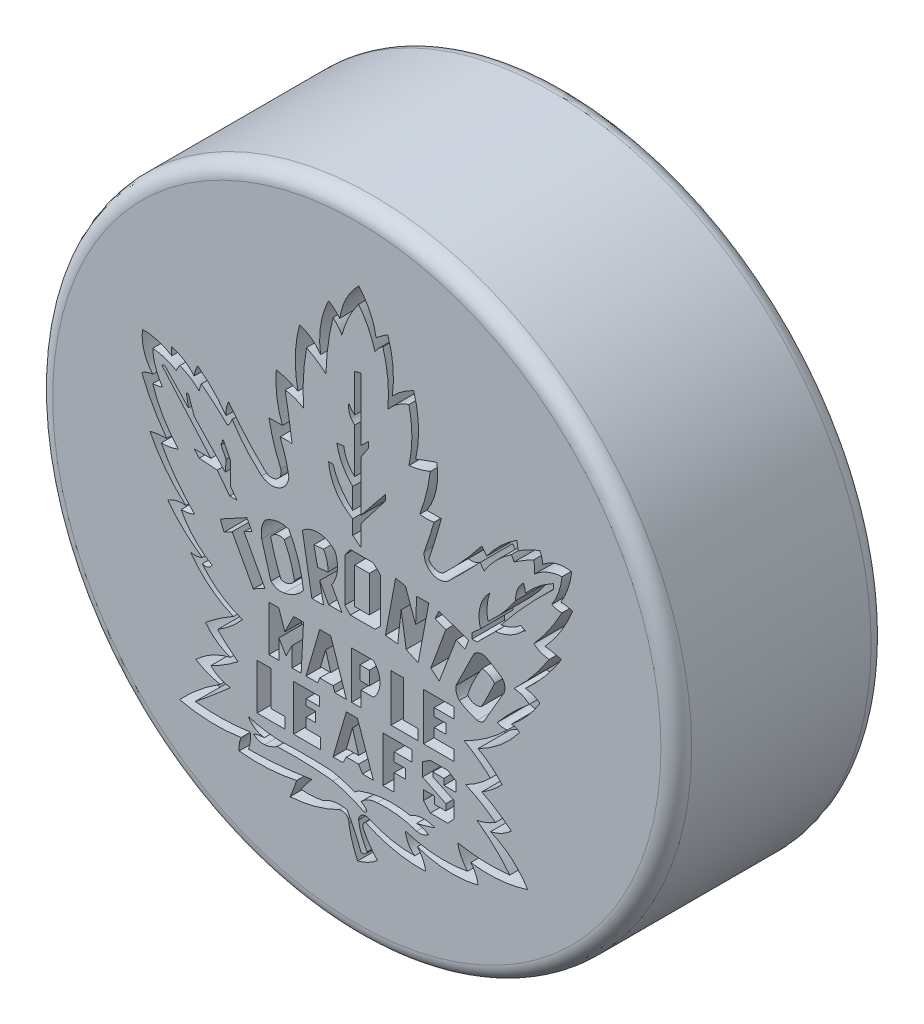
SolidWorks part; units mm, degrees
ref_plane "Front Plane" through (0, 0, 0) normal (0, 0, 1) x (1, 0, 0)
ref_plane "Top Plane" through (0, 0, 0) normal (0, 1, 0) x (1, 0, 0)
ref_plane "Right Plane" through (0, 0, 0) normal (1, 0, 0) x (0, 0, -1)
sketch "Sketch1" plane through (0, 0, 0) normal (0, 0, 1) x (1, 0, 0)
  line L0 (34.5, 121.5) -> (172.5, 121.5) construction
  line L1 (6.3057, 68.3336) -> (15.8951, 57.3506)
  line L6 (30.3167, 86.1583) -> (30.3167, 80.7546)
  line L7 (27.2525, 71.8253) -> (24.9367, 71.8253)
  line L8 (6.9514, 74.6669) -> (6.8534, 73.8865)
  line L9 (12.1754, 10.8034) -> (19.3568, 10.8034)
  line L10 (15.8951, 57.3506) -> (12.6238, 57.3506)
  line L11 (12.6238, 57.3506) -> (13.5994, 56.2333)
  line L12 (13.5994, 56.2333) -> (17.1344, 55.9938)
  line L13 (17.1344, 55.9938) -> (19.5676, 52.8135)
  line L14 (19.5676, 52.8135) -> (21.025, 52.8135)
  line L15 (21.025, 52.8135) -> (19.7407, 54.4922)
  line L16 (19.7407, 54.4922) -> (19.7407, 58.8908)
  line L17 (19.7407, 58.8908) -> (18.2642, 61.8099)
  line L18 (18.2642, 61.8099) -> (17.8765, 60.6287)
  line L19 (17.8765, 60.6287) -> (18.8654, 58.6737)
  line L20 (18.8654, 58.6737) -> (18.7132, 56.4273)
  line L21 (18.7132, 56.4273) -> (12.6238, 62.8421)
  line L22 (12.6238, 62.8421) -> (11.5036, 66.0747)
  line L25 (11.5036, 63.7081) -> (6.8096, 68.653)
  line L26 (6.8096, 68.653) -> (6.3057, 68.3336)
  line L27 (11.5036, 63.7081) -> (11.1004, 66.0747)
  line L28 (11.1004, 66.0747) -> (11.5036, 66.0747)
  line L29 (44.0339, 86.1583) -> (45.2677, 86.4828)
  line L30 (45.2677, 86.4828) -> (45.2677, 74.1922)
  line L31 (45.2677, 74.1922) -> (46.7323, 75.6568)
  line L32 (46.7323, 75.6568) -> (46.7323, 74.5052)
  line L33 (46.7323, 74.5052) -> (45.2677, 72.2648)
  line L34 (45.2677, 72.2648) -> (45.2677, 62.4102)
  line L35 (45.2677, 62.4102) -> (50.0411, 68.3336)
  line L36 (50.0411, 68.3336) -> (50.0411, 67.2036)
  line L37 (50.0411, 67.2036) -> (45.2677, 61.0086)
  line L38 (45.2677, 61.0086) -> (45.2677, 56.9127)
  line L39 (45.2677, 56.9127) -> (43.6367, 58.1694)
  line L40 (43.6367, 58.1694) -> (43.6367, 61.0086)
  line L41 (38.9245, 68.3336) -> (39.7941, 68.3336)
  line L42 (40.5155, 72.2648) -> (41.9224, 72.4343)
  line L43 (41.9224, 72.4343) -> (41.9224, 72.3332)
  line L44 (43.6367, 66.4741) -> (43.6367, 62.4102)
  line L45 (44.0339, 78.7841) -> (44.0339, 86.1583)
  line L46 (44.0339, 68.3336) -> (44.0339, 77.0681)
  line L48 (66.9786, 53.365) -> (66.9786, 52.2776)
  line L49 (66.9786, 52.2776) -> (67.9755, 52.2776)
  line L50 (67.9755, 52.2776) -> (71.5619, 55.8427)
  line L51 (66.9786, 53.365) -> (68.6517, 54.8561)
  line L52 (76.5056, 59.3605) -> (77.4165, 58.8908)
  line L53 (77.4165, 58.8908) -> (77.0329, 58.6853)
  line L54 (29.874, 69.9206) -> (27.2525, 69.9206)
  line L55 (17.7325, 48.0078) -> (22.922, 50.8265)
  line L56 (22.922, 50.8265) -> (23.9165, 48.9955)
  line L57 (23.9165, 48.9955) -> (22.3701, 48.1556)
  line L58 (22.3701, 48.1556) -> (26.4629, 40.6203)
  line L59 (26.4629, 40.6203) -> (24.1884, 39.3849)
  line L60 (24.1884, 39.3849) -> (20.0547, 46.9954)
  line L61 (20.0547, 46.9954) -> (18.4461, 46.1217)
  line L62 (18.4461, 46.1217) -> (17.7325, 48.0078)
  line L63 (42.0881, 54.1273) -> (42.0881, 45.5535)
  line L64 (42.0881, 45.5535) -> (43.1911, 44.4505)
  line L65 (43.1911, 44.4505) -> (48.0086, 44.4505)
  line L66 (48.0086, 44.4505) -> (49.1116, 45.5535)
  line L67 (49.1116, 45.5535) -> (49.1116, 54.1273)
  line L68 (49.1116, 54.1273) -> (47.6913, 55.5476)
  line L69 (47.6913, 55.5476) -> (43.1911, 55.5476)
  line L70 (43.1911, 55.5476) -> (42.0881, 54.1273)
  line L71 (44.0339, 53.365) -> (46.8868, 53.365)
  line L72 (46.8868, 53.365) -> (46.8868, 46.3139)
  line L73 (46.8868, 46.3139) -> (44.0339, 46.3139)
  line L74 (44.0339, 46.3139) -> (44.0339, 53.365)
  line L75 (33.7917, 54.1273) -> (35.6496, 43.498)
  line L76 (35.6496, 43.498) -> (37.933, 43.498)
  line L77 (37.933, 43.498) -> (37.1838, 47.2971)
  line L78 (37.1838, 47.2971) -> (38.9245, 44.0735)
  line L79 (38.9245, 44.0735) -> (41.5213, 44.0735)
  line L80 (41.5213, 44.0735) -> (39.5306, 47.7599)
  line L81 (36.0392, 52.7859) -> (36.7945, 49.3156)
  line L82 (36.7945, 49.3156) -> (38.7916, 49.5311)
  line L83 (36.0392, 52.7859) -> (37.933, 52.9837)
  line L84 (25.8383, 48.6827) -> (27.6283, 42.4266)
  line L85 (50.0411, 44.4505) -> (52.0362, 55.1267)
  line L86 (52.0362, 55.1267) -> (53.9533, 54.7684)
  line L87 (53.9533, 54.7684) -> (55.9534, 49.2355)
  line L88 (55.9534, 49.2355) -> (56.144, 54.1273)
  line L89 (56.144, 54.1273) -> (58.5251, 54.1273)
  line L90 (58.5251, 54.1273) -> (56.4417, 42.9794)
  line L91 (56.4417, 42.9794) -> (54.1026, 44.0735)
  line L92 (54.1026, 44.0735) -> (53.1196, 50.3069)
  line L93 (53.1196, 50.3069) -> (52.4464, 44.1881)
  line L94 (52.4464, 44.1881) -> (50.0411, 44.4505)
  line L96 (66.3288, 51.7517) -> (65.6176, 49.8908)
  line L97 (65.6176, 49.8908) -> (63.8591, 50.5629)
  line L98 (63.8591, 50.5629) -> (60.5679, 41.9509)
  line L99 (60.5679, 41.9509) -> (58.9206, 43.3234)
  line L100 (58.9206, 43.3234) -> (61.8601, 51.3268)
  line L101 (61.8601, 51.3268) -> (59.7442, 52.1039)
  line L103 (59.7442, 52.1039) -> (60.5123, 53.7569)
  line L104 (60.5123, 53.7569) -> (66.3288, 51.7517)
  line L105 (63.8591, 42.8783) -> (67.3185, 49.8908)
  line L106 (69.358, 39.5777) -> (73.2604, 46.3139)
  line L107 (27.2525, 29.7743) -> (27.2525, 38.6676)
  line L108 (27.2525, 38.6676) -> (29.1958, 38.6676)
  line L109 (29.1958, 38.6676) -> (30.3678, 35.2087)
  line L110 (30.3678, 35.2087) -> (32.0759, 38.6676)
  line L111 (32.0759, 38.6676) -> (34.0127, 38.6676)
  line L112 (34.0127, 38.6676) -> (33.5534, 29.7743)
  line L113 (33.5534, 29.7743) -> (31.7771, 29.7743)
  line L114 (31.7771, 29.7743) -> (31.7771, 33.586)
  line L115 (31.7771, 33.586) -> (30.6072, 31.2168)
  line L116 (30.6072, 31.2168) -> (29.1958, 33.586)
  line L117 (29.1958, 33.586) -> (29.1958, 29.7743)
  line L118 (29.1958, 29.7743) -> (27.2525, 29.7743)
  line L119 (34.4991, 29.7743) -> (36.7945, 29.7743)
  line L120 (36.7945, 29.7743) -> (37.1838, 30.7878)
  line L121 (37.1838, 30.7878) -> (39.7941, 30.7878)
  line L122 (39.7941, 30.7878) -> (40.1678, 29.7743)
  line L123 (40.1678, 29.7743) -> (42.3991, 29.7743)
  line L124 (42.3991, 29.7743) -> (39.3473, 39.0131)
  line L125 (39.3473, 39.0131) -> (37.1838, 39.0131)
  line L126 (37.1838, 39.0131) -> (34.4991, 29.7743)
  line L127 (37.3474, 32.7715) -> (39.3473, 32.7715)
  line L128 (39.3473, 32.7715) -> (38.3474, 36.1374)
  line L129 (38.3474, 36.1374) -> (37.3474, 32.7715)
  line L130 (43.4149, 29.7743) -> (43.4149, 39.0131)
  line L131 (43.4149, 39.0131) -> (47.6913, 39.0131)
  line L132 (43.4149, 29.7743) -> (45.2399, 29.7743)
  line L133 (45.2399, 29.7743) -> (45.2399, 32.7715)
  line L134 (45.2399, 32.7715) -> (47.6913, 32.7715)
  line L135 (51.1553, 39.0131) -> (53.5887, 39.0131)
  line L136 (45.0765, 36.9598) -> (46.8868, 36.9598)
  line L137 (45.0765, 36.9598) -> (45.0765, 34.2952)
  line L138 (45.0765, 34.2952) -> (46.8868, 34.2952)
  line L139 (46.8868, 36.9598) -> (46.8868, 34.2952)
  line L140 (53.5887, 39.0131) -> (53.5887, 31.8324)
  line L141 (53.5887, 31.8324) -> (56.4417, 31.8324)
  line L145 (51.1553, 39.0131) -> (51.1553, 29.7743)
  line L146 (51.1553, 29.7743) -> (56.4417, 29.7743)
  line L147 (56.4417, 29.7743) -> (56.4417, 31.8324)
  line L148 (57.4755, 29.7743) -> (63.4335, 29.7743)
  line L149 (63.4335, 29.7743) -> (63.4335, 31.8324)
  line L150 (63.4335, 31.8324) -> (59.5649, 31.8324)
  line L151 (59.5649, 31.8324) -> (59.5649, 33.586)
  line L152 (59.5649, 33.586) -> (61.8601, 33.586)
  line L153 (61.8601, 33.586) -> (61.8601, 35.4618)
  line L154 (61.8601, 35.4618) -> (59.5649, 35.4618)
  line L155 (59.5649, 35.4618) -> (59.5649, 36.9598)
  line L156 (59.5649, 36.9598) -> (63.4335, 36.9598)
  line L157 (63.4335, 36.9598) -> (63.4335, 39.0131)
  line L158 (63.4335, 39.0131) -> (57.4755, 39.0131)
  line L159 (57.4755, 39.0131) -> (57.4755, 29.7743)
  line L160 (24.9367, 27.6583) -> (27.6283, 27.6583)
  line L161 (27.6283, 27.6583) -> (27.6283, 20.8444)
  line L162 (27.6283, 20.8444) -> (30.3678, 20.8444)
  line L163 (30.3678, 20.8444) -> (30.3678, 18.7141)
  line L164 (30.3678, 18.7141) -> (24.9367, 18.7141)
  line L165 (24.9367, 18.7141) -> (24.9367, 27.6583)
  line L166 (32.0759, 27.6583) -> (32.0759, 18.7141)
  line L167 (32.0759, 18.7141) -> (37.3474, 18.7141)
  line L168 (37.3474, 18.7141) -> (37.3474, 20.8444)
  line L169 (37.3474, 20.8444) -> (34.4991, 20.8444)
  line L170 (34.4991, 20.8444) -> (34.4991, 22.8011)
  line L171 (34.4991, 22.8011) -> (36.3392, 22.8011)
  line L172 (36.3392, 22.8011) -> (36.3392, 24.7422)
  line L173 (36.3392, 24.7422) -> (34.4991, 24.7422)
  line L174 (34.4991, 24.7422) -> (34.4991, 25.9294)
  line L175 (34.4991, 25.9294) -> (37.1838, 25.9294)
  line L176 (37.1838, 25.9294) -> (37.1838, 27.6583)
  line L177 (37.1838, 27.6583) -> (32.0759, 27.6583)
  line L178 (39.7941, 18.7141) -> (41.7277, 18.7141)
  line L179 (41.7277, 18.7141) -> (42.3991, 19.9957)
  line L180 (42.3991, 19.9957) -> (44.7952, 19.9957)
  line L181 (44.7952, 19.9957) -> (45.5443, 18.7141)
  line L182 (45.5443, 18.7141) -> (47.6913, 18.7141)
  line L183 (44.5704, 27.6583) -> (47.6913, 18.7141)
  line L184 (39.7941, 18.7141) -> (42.3991, 27.6583)
  line L185 (42.3991, 27.6583) -> (44.5704, 27.6583)
  line L186 (42.3991, 21.453) -> (44.7952, 21.453)
  line L187 (44.7952, 21.453) -> (43.5971, 25.5575)
  line L188 (43.5971, 25.5575) -> (42.3991, 21.453)
  line L189 (49.5479, 18.7141) -> (49.5479, 27.6583)
  line L190 (49.5479, 27.6583) -> (55.2493, 27.6583)
  line L191 (55.2493, 27.6583) -> (55.2493, 25.5575)
  line L192 (55.2493, 25.5575) -> (51.7544, 25.5575)
  line L193 (51.7544, 25.5575) -> (51.7544, 23.847)
  line L194 (51.7544, 23.847) -> (53.9533, 23.847)
  line L195 (53.9533, 23.847) -> (53.9533, 22.028)
  line L196 (53.9533, 22.028) -> (51.7544, 22.028)
  line L197 (51.7544, 22.028) -> (51.7544, 18.7141)
  line L198 (51.7544, 18.7141) -> (49.5479, 18.7141)
  line L199 (57.4755, 22.028) -> (59.6905, 22.028)
  line L200 (61.4891, 24.7422) -> (63.8591, 24.7422)
  line L201 (58.8218, 27.6583) -> (62.2386, 27.6583)
  line L202 (57.2969, 24.067) -> (57.2969, 26.6528)
  line L203 (58.8218, 18.7141) -> (62.2386, 18.7141)
  line L204 (63.4335, 23.1835) -> (63.4335, 19.9957)
  line L205 (63.8591, 24.7422) -> (63.8591, 26.6528)
  line L206 (57.4755, 22.028) -> (57.4755, 20.164)
  line L207 (57.4755, 20.164) -> (58.8218, 18.7141)
  line L208 (62.2386, 18.7141) -> (63.4335, 19.9957)
  line L209 (57.2969, 26.6528) -> (58.8218, 27.6583)
  line L210 (62.2386, 27.6583) -> (63.8591, 26.6528)
  line L211 (57.2969, 24.067) -> (61.8601, 21.8277)
  line L212 (61.8601, 21.8277) -> (61.8601, 20.5939)
  line L213 (61.8601, 20.5939) -> (59.6905, 20.5939)
  line L214 (59.6905, 20.5939) -> (59.6905, 22.028)
  line L215 (61.4891, 24.7422) -> (61.4652, 25.9294)
  line L216 (61.4652, 25.9294) -> (59.3097, 25.9294)
  line L219 (63.4335, 23.1835) -> (59.3097, 25.1115)
  line L220 (59.3097, 25.1115) -> (59.3097, 25.9294)
  arc A0 (39.953, 97.4839) -> (44.45, 104.2073) centre (59.6905, 89.1481) cw
  arc A1 (37.8969, 99.1631) -> (39.953, 97.4839) centre (41.9224, 101.9937) ccw
  arc A2 (37.8969, 99.1631) -> (35.4553, 90.046) centre (55.567, 89.5455) ccw
  arc A3 (35.4553, 90.046) -> (31.7771, 91.4752) centre (63.8591, 168.5955) cw
  arc A4 (31.7771, 91.4752) -> (30.3167, 86.1583) centre (42.5693, 85.652) ccw
  arc A5 (26.4126, 81.5637) -> (30.3167, 80.7546) centre (32.5268, 101.2426) ccw
  arc A6 (26.4126, 81.5637) -> (27.2525, 71.8253) centre (51.0633, 78.7841) ccw
  arc A7 (24.9367, 71.8253) -> (27.2525, 63.058) centre (47.3507, 73.056) ccw
  arc A8 (18.2642, 73.6371) -> (27.2525, 63.058) centre (72.867, 110.9209) ccw
  arc A9 (18.2642, 73.6371) -> (17.4501, 71.228) centre (25.2907, 69.9206) ccw
  arc A10 (12.0805, 74.6669) -> (17.4501, 71.228) centre (4.7765, 57.3506) cw
  arc A11 (12.0805, 74.6669) -> (11.3954, 73.4241) centre (15.8951, 71.7539) ccw
  arc A12 (6.9514, 74.6669) -> (11.3954, 73.4241) centre (6.8096, 65.5926) cw
  arc A13 (0.6356, 74.6669) -> (6.8534, 73.8865) centre (2.0793, 61.0086) cw
  arc A14 (0.6356, 74.6669) -> (0.6356, 68.9794) centre (18.0812, 71.8231) ccw
  arc A15 (0.6356, 68.9794) -> (1.5259, 67.2036) centre (5.7551, 70.4349) ccw
  arc A16 (1.5259, 67.2036) -> (0, 65.9359) centre (-1.3367, 69.0971) cw
  arc A17 (0, 65.9359) -> (3.7896, 58.1694) centre (24.1015, 72.8882) ccw
  arc A18 (3.7896, 58.1694) -> (0.8565, 56.9127) centre (-0.9293, 65.1323) cw
  arc A19 (0.8565, 56.9127) -> (6.8534, 48.2966) centre (72.2331, 100.1966) ccw
  arc A20 (4.382, 46.7197) -> (6.8534, 48.2966) centre (3.1638, 51.3542) ccw
  arc A21 (4.382, 46.7197) -> (9.7464, 40.6203) centre (24.3706, 58.8908) ccw
  arc A22 (8.2378, 39.8005) -> (9.7464, 40.6203) centre (4.518, 48.4431) ccw
  arc A23 (8.2378, 39.8005) -> (15.8951, 32.601) centre (33.1958, 58.6737) ccw
  arc A24 (12.0805, 28.814) -> (15.8951, 32.601) centre (29.9388, 14.6403) cw
  arc A25 (12.0805, 28.814) -> (15.0982, 25.9294) centre (0.9087, 14.1061) cw
  arc A26 (15.0982, 25.9294) -> (9.539, 21.2972) centre (30.9827, 1.214) ccw
  arc A27 (9.539, 21.2972) -> (12.8259, 19.2826) centre (4.6564, 9.6427) cw
  arc A28 (6.3057, 12.3095) -> (12.8259, 19.2826) centre (24.2625, 2.0539) cw
  arc A29 (6.3057, 12.3095) -> (12.1754, 10.8034) centre (12.6238, 24.7422) ccw
  arc A30 (19.3568, 10.8034) -> (19.1163, 8.4963) centre (14.9335, 10.0985) cw
  arc A31 (19.1163, 8.4963) -> (29.5823, 8.709) centre (23.5846, 46.2274) ccw
  arc A32 (29.5823, 8.709) -> (29.5823, 5.9712) centre (26.3569, 7.3401) cw
  arc A33 (29.5823, 5.9712) -> (40.5155, 8.4963) centre (31.1057, 24.307) ccw
  arc A34 (44.45, 104.2073) -> (49.5479, 97.4839) centre (34.0638, 91.0379) cw
  arc A35 (49.5479, 97.4839) -> (51.7544, 98.4025) centre (49.2697, 101.2615) ccw
  arc A36 (51.7544, 98.4025) -> (54.1026, 90.4118) centre (29.874, 87.6322) cw
  arc A37 (54.1026, 90.4118) -> (56.6792, 91.4752) centre (64.492, 68.8911) cw
  arc A38 (56.6792, 91.4752) -> (58.8218, 80.7546) centre (39.7941, 82.5261) cw
  arc A39 (58.8218, 80.7546) -> (62.2386, 81.5637) centre (59.177, 86.8735) ccw
  arc A40 (62.2386, 81.5637) -> (61.3432, 72.2648) centre (46.7323, 78.3642) cw
  arc A41 (61.3432, 72.2648) -> (63.4335, 72.2648) centre (62.3883, 74.5052) ccw
  arc A42 (63.4335, 72.2648) -> (61.3432, 63.058) centre (30.4249, 74.9185) cw
  arc A43 (61.3432, 63.058) -> (70.3121, 73.4241) centre (191.3667, -40.3773) cw
  arc A44 (70.3121, 73.4241) -> (70.4669, 72.2648) centre (68.2918, 72.5643) cw
  arc A45 (70.4669, 72.2648) -> (76.5056, 76.3413) centre (82.9428, 60.2945) cw
  arc A46 (76.5056, 76.3413) -> (77.0329, 75.0266) centre (74.6899, 74.8498) cw
  arc A47 (77.0329, 75.0266) -> (82.0829, 76.0779) centre (82.8066, 59.947) cw
  arc A48 (82.0829, 76.0779) -> (82.1237, 75.169) centre (74.3776, 75.2768) cw
  arc A49 (82.1237, 75.169) -> (88.49, 75.6241) centre (86.1081, 64.1877) cw
  arc A50 (88.49, 75.6241) -> (87.2683, 68.3336) centre (71.03, 74.8023) cw
  arc A51 (87.2683, 68.3336) -> (88.9, 67.4547) centre (87.1042, 66.0747) cw
  arc A52 (85.0576, 59.5877) -> (88.9, 67.4547) centre (66.3288, 73.6069) ccw
  arc A53 (85.0576, 59.5877) -> (87.6244, 58.7299) centre (89.2132, 67.7531) ccw
  arc A54 (81.198, 49.8492) -> (87.6244, 58.7299) centre (34.0127, 90.7599) ccw
  arc A55 (81.198, 49.8492) -> (83.0778, 48.2194) centre (75.7967, 41.7206) cw
  arc A56 (78.1618, 42.4266) -> (83.0778, 48.2194) centre (58.9206, 63.7376) ccw
  arc A57 (78.1618, 42.4266) -> (79.005, 41.4927) centre (79.0503, 42.3812) ccw
  arc A58 (79.005, 41.4927) -> (71.9204, 34.2952) centre (63.0636, 50.0984) cw
  arc A59 (71.9204, 34.2952) -> (75.7967, 30.2227) centre (58.1473, 17.3044) cw
  arc A60 (72.6556, 27.6583) -> (75.7967, 30.2227) centre (62.8474, 42.8783) ccw
  arc A61 (72.6556, 27.6583) -> (77.4679, 23.847) centre (61.9836, 9.2398) cw
  arc A62 (74.6899, 21.2972) -> (77.4679, 23.847) centre (68.1498, 31.2112) ccw
  arc A63 (74.6899, 21.2972) -> (80.8123, 14.6403) centre (67.3185, 8.3739) cw
  arc A64 (70.3121, 12.3095) -> (80.8123, 14.6403) centre (72.2864, 28.2321) ccw
  arc A65 (60.2753, 8.709) -> (70.4669, 10.0985) centre (62.6359, 29.4655) ccw
  arc A66 (70.3121, 12.3095) -> (70.4669, 10.0985) centre (78.1512, 11.7475) ccw
  arc A67 (60.2753, 8.709) -> (61.0619, 6.7442) centre (64.4973, 9.2592) ccw
  arc A68 (49.5479, 7.3401) -> (61.0619, 6.7442) centre (57.1649, 42.9794) ccw
  arc A69 (49.5479, 7.3401) -> (51.7544, 5.4046) centre (58.4524, 15.266) ccw
  arc A70 (40.5155, 8.4963) -> (41.376, 7.6769) centre (40.536, 7.6564) cw
  arc A71 (41.376, 7.6769) -> (44.45, 0.3121) centre (53.5887, 8.4505) ccw
  arc A72 (44.45, 0.3121) -> (51.7544, 5.4046) centre (33.5534, 23.7265) ccw
  arc A73 (43.6367, 61.0086) -> (38.9245, 68.3336) centre (48.0086, 68.9992) cw
  arc A74 (39.7941, 68.3336) -> (43.6367, 62.4102) centre (52.4464, 72.3332) ccw
  arc A75 (40.5155, 72.2648) -> (43.6367, 66.4741) centre (51.1915, 74.2827) ccw
  arc A76 (41.9224, 72.3332) -> (44.0339, 68.3336) centre (48.4459, 73.22) ccw
  arc A77 (42.8971, 80.3015) -> (44.0339, 77.0681) centre (46.1509, 79.6289) ccw
  arc A78 (42.8971, 80.3015) -> (44.0339, 78.7841) centre (45.733, 81.2416) ccw
  arc A79 (68.6517, 54.8561) -> (70.4669, 61.8099) centre (75.1999, 56.8606) cw
  arc A80 (70.101, 56.8606) -> (70.4669, 61.8099) centre (79.0769, 58.6853) cw
  arc A81 (70.101, 56.8606) -> (75.5187, 63.058) centre (50.8202, 79.1822) ccw
  arc A82 (75.5187, 63.058) -> (77.0329, 66.7956) centre (80.2613, 63.3121) cw
  arc A83 (77.0329, 66.7956) -> (77.4165, 65.2735) centre (74.1185, 65.2517) cw
  arc A84 (77.4165, 65.2735) -> (82.9428, 69.6636) centre (91.8679, 52.7553) cw
  arc A85 (82.9428, 69.6636) -> (82.9428, 68.653) centre (91.7697, 69.1583) ccw
  arc A86 (82.9428, 68.653) -> (72.6556, 57.5455) centre (159.5754, -12.6376) ccw
  arc A87 (71.5619, 55.8427) -> (77.0329, 58.6853) centre (70.4486, 64.6718) ccw
  arc A88 (72.6556, 57.5455) -> (76.5056, 59.3605) centre (71.7707, 64.4135) ccw
  arc A89 (23.1917, 17.3044) -> (29.1958, 16.243) centre (30.2497, 39.7188) ccw
  arc A90 (23.1917, 17.3044) -> (26.3569, 15.266) centre (26.7477, 19.3496) ccw
  arc A91 (24.2011, 14.8338) -> (26.3569, 15.266) centre (26.6884, 8.0199) cw
  arc A92 (24.2011, 14.8338) -> (26.4126, 14.1061) centre (26.15, 17.0321) ccw
  arc A93 (26.4126, 14.1061) -> (28.8466, 14.9915) centre (25.8383, 19.4728) ccw
  arc A94 (28.8466, 14.9915) -> (39.7941, 14.6403) centre (32.1233, -53.6633) cw
  arc A95 (39.7941, 14.6403) -> (45.733, 12.4966) centre (34.6999, -8.7709) cw
  arc A96 (45.733, 12.4966) -> (46.4216, 12.84) centre (45.9056, 13.0126) ccw
  arc A97 (45.2677, 13.8729) -> (46.4216, 12.84) centre (44.0158, 11.3133) cw
  arc A98 (45.2677, 13.8729) -> (48.4459, 15.266) centre (48.5512, 10.7037) cw
  arc A99 (48.4459, 15.266) -> (56.144, 14.2945) centre (50.1038, -2.5822) cw
  arc A100 (56.144, 14.2945) -> (58.4524, 14.8619) centre (56.6713, 17.1288) ccw
  arc A101 (58.4524, 14.8619) -> (56.144, 15.6253) centre (56.2765, 12.1538) ccw
  arc A102 (56.144, 15.6253) -> (59.6905, 16.6676) centre (49.2746, 45.5535) ccw
  arc A103 (59.6905, 16.6676) -> (54.8834, 16.361) centre (57.5817, 11.8918) ccw
  arc A104 (45.2399, 15.6151) -> (54.8834, 16.361) centre (51.3871, -1.1493) cw
  arc A105 (45.2399, 15.6151) -> (44.0158, 14.8618) centre (46.484, 12.2222) ccw
  arc A106 (44.0158, 14.8618) -> (39.3473, 16.243) centre (36.0392, -3.5187) ccw
  arc A107 (29.1958, 16.243) -> (39.3473, 16.243) centre (34.2715, -88.6983) cw
  arc A108 (41.1071, 93.6951) -> (44.7952, 101.0181) centre (54.0654, 91.7591) cw
  arc A109 (41.1071, 93.6951) -> (38.9245, 95.6058) centre (33.2426, 86.9131) ccw
  arc A110 (38.9245, 95.6058) -> (37.3474, 85.652) centre (53.9533, 88.1227) ccw
  arc A111 (37.3474, 85.652) -> (33.2426, 88.6762) centre (31.1465, 81.5333) ccw
  arc A112 (33.2426, 88.6762) -> (32.9284, 77.2581) centre (56.9087, 82.3117) ccw
  arc A113 (29.874, 69.9206) -> (28.6937, 78.7841) centre (48.7818, 76.9488) cw
  arc A114 (28.6937, 78.7841) -> (32.9284, 77.2581) centre (25.5519, 63.4266) cw
  arc A115 (26.4126, 60.6287) -> (29.5823, 62.4102) centre (27.7758, 61.9138) ccw
  arc A116 (29.5823, 62.4102) -> (27.2525, 69.9206) centre (58.5251, 75.5051) cw
  arc A117 (26.4126, 60.6287) -> (19.3568, 68.653) centre (70.7595, 106.7371) cw
  arc A118 (18.8654, 66.0747) -> (19.3568, 68.653) centre (23.8409, 66.4623) cw
  arc A119 (18.8654, 66.0747) -> (13.313, 71.7539) centre (-1.6958, 51.5262) ccw
  arc A120 (13.313, 71.7539) -> (12.6238, 69.6636) centre (18.3307, 68.9409) ccw
  arc A121 (12.6238, 69.6636) -> (8.2378, 72.4343) centre (6.1876, 64.3318) ccw
  arc A122 (8.2378, 72.4343) -> (8.2378, 70.8974) centre (12.1478, 71.6658) ccw
  arc A123 (8.2378, 70.8974) -> (2.5118, 72.525) centre (2.5997, 61.948) ccw
  arc A124 (2.5118, 72.525) -> (4.518, 65.9359) centre (10.826, 71.4564) ccw
  arc A125 (2.3637, 65.1323) -> (4.518, 65.9359) centre (4.9076, 61.6023) cw
  arc A126 (2.3637, 65.1323) -> (7.2499, 56.4273) centre (37.933, 79.3738) ccw
  arc A127 (3.9571, 55.9938) -> (7.2499, 56.4273) centre (7.4699, 42.0351) cw
  arc A128 (3.9571, 55.9938) -> (10.9871, 46.9175) centre (30.3396, 69.1676) ccw
  arc A129 (7.4699, 46.0561) -> (10.9871, 46.9175) centre (10.3393, 41.9509) cw
  arc A130 (7.4699, 46.0561) -> (14.2015, 39.7188) centre (29.4197, 62.6275) ccw
  arc A131 (14.2015, 39.7188) -> (11.919, 39.4664) centre (12.6902, 42.9388) cw
  arc A132 (11.919, 39.4664) -> (20.3138, 32.7715) centre (27.6283, 50.5537) ccw
  arc A133 (14.8465, 29.0375) -> (20.3138, 32.7715) centre (38.3993, 0.4212) cw
  arc A134 (14.8465, 29.0375) -> (19.7407, 25.5575) centre (22.6986, 34.8989) ccw
  arc A135 (12.9629, 21.8277) -> (19.7407, 25.5575) centre (23.2443, 11.1673) cw
  arc A136 (12.9629, 21.8277) -> (17.7325, 19.9957) centre (19.7074, 32.262) ccw
  arc A137 (9.7464, 13.4212) -> (17.7325, 19.9957) centre (39.8196, -14.9717) cw
  arc A138 (9.7464, 13.4212) -> (21.8035, 13.0126) centre (16.8207, 44.0735) ccw
  arc A139 (21.8035, 13.0126) -> (21.4197, 10.539) centre (26.5448, 11.0104) ccw
  arc A140 (21.4197, 10.539) -> (32.6724, 11.1673) centre (25.1455, 44.89) ccw
  arc A141 (32.6724, 11.1673) -> (31.397, 7.7771) centre (-3.4135, 22.8077) cw
  arc A142 (31.397, 7.7771) -> (40.9974, 10.3912) centre (29.8809, 32.2813) ccw
  arc A143 (40.9974, 10.3912) -> (42.8971, 8.9883) centre (41.5213, 9.1129) cw
  arc A144 (42.8971, 8.9883) -> (44.6005, 3.4896) centre (62.7339, 12.1204) ccw
  arc A145 (45.733, 9.457) -> (48.4826, 5.4981) centre (60.4844, 16.768) ccw
  arc A146 (44.6005, 3.4896) -> (48.4826, 5.4981) centre (42.0881, 13.1016) ccw
  arc A147 (46.1509, 10.8034) -> (57.9289, 8.3739) centre (56.8939, 33.1202) ccw
  arc A148 (57.9289, 8.3739) -> (56.2765, 11.7475) centre (51.8457, 7.4858) ccw
  arc A149 (56.2765, 11.7475) -> (68.1498, 11.1673) centre (63.1787, 31.2168) ccw
  arc A150 (66.7337, 14.2945) -> (68.1498, 11.1673) centre (62.6015, 10.5391) cw
  arc A151 (66.7337, 14.2945) -> (77.8863, 15.266) centre (70.1991, 39.0131) ccw
  arc A152 (77.8863, 15.266) -> (70.6118, 21.453) centre (64.7964, 7.2454) ccw
  arc A153 (70.6118, 21.453) -> (74.6899, 23.5928) centre (68.5725, 30.2957) ccw
  arc A154 (68.8841, 27.3392) -> (74.6899, 23.5928) centre (57.1113, 2.7232) cw
  arc A155 (68.8841, 27.3392) -> (72.867, 30.542) centre (59.3097, 43.3234) ccw
  arc A156 (72.867, 30.542) -> (68.1498, 34.2952) centre (60.9825, 20.4457) ccw
  arc A157 (68.1498, 34.2952) -> (76.2947, 41.065) centre (57.7212, 55.1267) ccw
  arc A158 (76.2947, 41.065) -> (74.6899, 41.7206) centre (74.7507, 39.5777) ccw
  arc A159 (74.6899, 41.7206) -> (80.2613, 48.0078) centre (60.1125, 60.2507) ccw
  arc A160 (80.2613, 48.0078) -> (77.4165, 49.1402) centre (77.093, 44.1881) ccw
  arc A161 (77.4165, 49.1402) -> (84.4931, 57.5455) centre (50.746, 78.7761) ccw
  arc A162 (84.4931, 57.5455) -> (81.2458, 58.1694) centre (80.0337, 43.097) ccw
  arc A163 (81.2458, 58.1694) -> (86.6347, 66.7956) centre (60.763, 76.9619) ccw
  arc A164 (86.6347, 66.7956) -> (84.3381, 67.2036) centre (84.6037, 62.0315) ccw
  arc A165 (84.3381, 67.2036) -> (86.4969, 73.4241) centre (71.2291, 75.2379) ccw
  arc A166 (86.4969, 73.4241) -> (80.8123, 71.8253) centre (85.2527, 66.9426) ccw
  arc A167 (80.8123, 71.8253) -> (80.2613, 73.8865) centre (76.4334, 71.7591) ccw
  arc A168 (80.2613, 73.8865) -> (76.0726, 71.7591) centre (85.252, 58.8727) ccw
  arc A169 (69.8401, 67.7531) -> (75.7967, 73.4241) centre (87.7087, 54.9485) cw
  arc A170 (75.7967, 73.4241) -> (76.0726, 71.7591) centre (81.517, 73.5163) ccw
  arc A171 (61.3432, 60.6287) -> (68.8841, 68.9992) centre (11.0265, 113.5405) ccw
  arc A172 (68.8841, 68.9992) -> (69.8401, 67.7531) centre (64.9916, 65.023) cw
  arc A173 (61.3432, 60.6287) -> (58.5251, 61.6023) centre (60.4209, 62.5246) cw
  arc A174 (58.5251, 61.6023) -> (60.9825, 69.6636) centre (-61.6421, 102.6406) ccw
  arc A175 (58.1473, 69.6636) -> (60.9825, 69.6636) centre (59.5649, 35.4618) cw
  arc A176 (58.1473, 69.6636) -> (60.1125, 78.7841) centre (47.3046, 76.7719) ccw
  arc A177 (55.9534, 77.2581) -> (60.1125, 78.7841) centre (87.9513, -3.5221) cw
  arc A178 (55.9534, 77.2581) -> (55.567, 88.6762) centre (34.6088, 82.2514) ccw
  arc A179 (51.3871, 85.652) -> (55.567, 88.6762) centre (61.4891, 76.0905) cw
  arc A180 (51.3871, 85.652) -> (50.507, 95.6058) centre (29.8741, 88.7655) ccw
  arc A181 (48.2115, 93.9465) -> (50.507, 95.6058) centre (62.7955, 76.1878) cw
  arc A182 (44.7952, 101.0181) -> (48.2115, 93.9465) centre (35.0408, 91.9448) cw
  arc A183 (25.8383, 59.3605) -> (31.1465, 61.9138) centre (27.8279, 62.0187) ccw
  arc A184 (31.1465, 61.9138) -> (29.4197, 67.7531) centre (5.7628, 57.5821) ccw
  arc A185 (29.4197, 67.7531) -> (31.7771, 67.7531) centre (30.5984, 60.7145) cw
  arc A186 (31.7771, 67.7531) -> (30.4249, 76.1878) centre (-160.4124, 41.2679) ccw
  arc A187 (30.4249, 76.1878) -> (34.0127, 74.9185) centre (29.6111, 68.1815) cw
  arc A188 (34.0127, 74.9185) -> (34.6088, 85.4791) centre (78.1275, 77.7258) cw
  arc A189 (34.6088, 85.4791) -> (38.3993, 82.9423) centre (25.6126, 67.9369) cw
  arc A190 (38.3993, 82.9423) -> (39.7941, 93.1818) centre (85.3584, 81.7601) cw
  arc A191 (39.7941, 93.1818) -> (41.5213, 91.0379) centre (34.8581, 87.4376) cw
  arc A192 (41.5213, 91.0379) -> (44.7952, 97.9056) centre (60.1507, 86.3711) cw
  arc A193 (44.7952, 97.9056) -> (48.0086, 91.4752) centre (29.7658, 86.3771) cw
  arc A194 (48.0086, 91.4752) -> (49.5479, 93.093) centre (52.0362, 89.1842) cw
  arc A195 (49.5479, 93.093) -> (50.507, 82.9423) centre (24.2639, 85.5833) cw
  arc A196 (50.507, 82.9423) -> (54.6429, 85.8638) centre (57.637, 77.2369) cw
  arc A197 (54.6429, 85.8638) -> (54.6429, 75.5051) centre (31.7976, 80.6845) cw
  arc A198 (54.6429, 75.5051) -> (58.8218, 76.5945) centre (52.694, 91.5402) ccw
  arc A199 (58.8218, 76.5945) -> (56.7689, 68.3336) centre (22.922, 81.1303) cw
  arc A200 (56.7689, 68.3336) -> (59.5649, 68.3692) centre (58.0809, 75.1066) ccw
  arc A201 (59.5649, 68.3692) -> (57.637, 62.4102) centre (-63.7499, 104.9728) cw
  arc A202 (57.637, 62.4102) -> (62.7955, 60.2507) centre (60.5123, 62.0375) ccw
  arc A203 (62.7955, 60.2507) -> (68.5725, 66.0747) centre (-22.2233, 150.3595) ccw
  arc A204 (68.5725, 66.0747) -> (69.358, 65.023) centre (78.0296, 72.3194) ccw
  arc A205 (69.358, 65.023) -> (74.6899, 70.4349) centre (84.8579, 55.0847) cw
  arc A206 (74.6899, 70.4349) -> (75.1999, 69.442) centre (71.1785, 68.0038) cw
  arc A207 (75.1999, 69.442) -> (79.0769, 71.7591) centre (97.0568, 37.2727) cw
  arc A208 (79.0769, 71.7591) -> (79.1709, 69.3506) centre (69.9032, 70.1953) cw
  arc A209 (79.1709, 69.3506) -> (84.6037, 71.6658) centre (85.132, 62.8941) cw
  arc A210 (82.5945, 65.9359) -> (84.6037, 71.6658) centre (71.9626, 72.8814) ccw
  arc A211 (82.5945, 65.9359) -> (84.6037, 65.5397) centre (84.2717, 69.1487) ccw
  arc A212 (79.0769, 57.5455) -> (84.6037, 65.5397) centre (48.0948, 84.8726) ccw
  arc A213 (79.0769, 57.5455) -> (82.0762, 56.3769) centre (82.3851, 61.603) ccw
  arc A214 (75.1999, 48.0078) -> (82.0762, 56.3769) centre (45.668, 79.2816) ccw
  arc A215 (75.1999, 48.0078) -> (78.1618, 46.7935) centre (75.1825, 43.7458) cw
  arc A216 (71.9204, 40.6203) -> (78.1618, 46.7935) centre (109.5068, 8.8603) cw
  arc A217 (71.9204, 40.6203) -> (73.9221, 40.3537) centre (73.2604, 43.0331) ccw
  arc A218 (65.4717, 34.2952) -> (73.9221, 40.3537) centre (51.1553, 63.1862) ccw
  arc A219 (65.4717, 34.2952) -> (70.6118, 30.542) centre (48.2467, 5.308) cw
  arc A220 (65.7322, 26.9981) -> (70.6118, 30.542) centre (57.4755, 43.498) ccw
  arc A221 (65.7322, 26.9981) -> (71.5619, 23.4874) centre (55.6456, 3.6531) cw
  arc A222 (67.9755, 22.028) -> (71.5619, 23.4874) centre (65.458, 33.3513) ccw
  arc A223 (67.9755, 22.028) -> (74.3776, 15.9884) centre (50.7182, -2.6779) cw
  arc A224 (74.3776, 15.9884) -> (64.1753, 16.361) centre (70.4839, 49.2355) cw
  arc A225 (64.1753, 16.361) -> (66.1205, 12.4966) centre (72.1088, 17.9326) ccw
  arc A226 (53.9533, 13.2435) -> (66.1205, 12.4966) centre (61.4652, 36.1374) ccw
  arc A227 (53.9533, 13.2435) -> (55.7775, 9.96) centre (58.4856, 13.613) ccw
  arc A228 (46.8868, 11.7475) -> (55.7775, 9.96) centre (55.2493, 30.3366) ccw
  arc A229 (44.7952, 10.5391) -> (46.8868, 11.7475) centre (46.2188, 10.4894) cw
  arc A230 (44.7952, 10.5391) -> (46.484, 5.9712) centre (55.4649, 11.8877) ccw
  arc A231 (45.2677, 5.308) -> (46.484, 5.9712) centre (45.5443, 6.2478) ccw
  arc A232 (45.2677, 5.308) -> (42.5693, 11.1073) centre (6.1797, -9.3518) ccw
  arc A233 (42.5693, 11.1073) -> (37.933, 10.3774) centre (41.0724, 5.5258) ccw
  arc A234 (33.5534, 10.0985) -> (35.6496, 12.84) centre (57.5016, -6.0411) cw
  arc A235 (33.5534, 10.0985) -> (37.933, 10.3774) centre (34.9433, 22.8011) ccw
  arc A236 (23.2443, 11.7475) -> (35.6496, 12.84) centre (22.7065, 88.8279) ccw
  arc A237 (23.2443, 11.7475) -> (23.5846, 14.8338) centre (17.0314, 13.9944) ccw
  arc A238 (23.5846, 14.8338) -> (12.8259, 14.6226) centre (17.4038, 55.5476) cw
  arc A239 (12.8259, 14.6226) -> (19.7407, 20.4457) centre (-90.1776, 143.9521) ccw
  arc A240 (19.7407, 20.4457) -> (15.8951, 22.2443) centre (20.0547, 26.1276) cw
  arc A241 (15.8951, 22.2443) -> (21.2181, 25.5575) centre (2.6038, 49.5311) ccw
  arc A242 (21.2181, 25.5575) -> (17.2222, 29.0375) centre (36.3392, 46.9546) cw
  arc A243 (17.2222, 29.0375) -> (22.0774, 33.1202) centre (7.2809, 45.7882) ccw
  arc A244 (22.0774, 33.1202) -> (14.2015, 38.6676) centre (27.5931, 49.3156) cw
  arc A245 (14.2015, 38.6676) -> (16.1175, 39.3849) centre (14.8009, 39.9842) ccw
  arc A246 (16.1175, 39.3849) -> (10.0802, 45.7882) centre (23.9165, 52.7859) cw
  arc A247 (10.0802, 45.7882) -> (12.6902, 46.3139) centre (10.3631, 51.1255) ccw
  arc A248 (12.6902, 46.3139) -> (6.1876, 55.1267) centre (38.2724, 71.9954) cw
  arc A249 (6.1876, 55.1267) -> (9.539, 55.7273) centre (6.4331, 63.4068) ccw
  arc A250 (9.539, 55.7273) -> (4.518, 64.3318) centre (26.0882, 71.1516) cw
  arc A251 (4.518, 64.3318) -> (6.4331, 64.6718) centre (4.0675, 72.4332) ccw
  arc A252 (6.4331, 64.6718) -> (4.518, 70.322) centre (15.2822, 70.8208) cw
  arc A253 (4.518, 70.322) -> (9.1041, 68.856) centre (3.6272, 59.6288) cw
  arc A254 (9.1041, 68.856) -> (9.8032, 70.0337) centre (15.0742, 66.1087) cw
  arc A255 (9.8032, 70.0337) -> (13.5994, 67.5982) centre (6.3922, 60.5408) cw
  arc A256 (13.5994, 67.5982) -> (14.0145, 69.0309) centre (20.9701, 66.2393) cw
  arc A257 (14.0145, 69.0309) -> (19.132, 64.5939) centre (-20.3297, 24.249) cw
  arc A258 (19.132, 64.5939) -> (20.0547, 66.0582) centre (17.3263, 66.7547) ccw
  arc A259 (20.0547, 66.0582) -> (25.8383, 59.3605) centre (44.7191, 81.5107) ccw
  arc A260 (33.7917, 54.1273) -> (40.1678, 53.7569) centre (36.7945, 50.7541) cw
  arc A261 (40.1678, 53.7569) -> (39.5306, 47.7599) centre (34.4991, 51.3268) cw
  arc A262 (37.933, 52.9837) -> (38.7916, 49.5311) centre (32.793, 49.8724) cw
  arc A263 (25.8383, 48.6827) -> (26.4126, 52.1038) centre (30.6443, 49.6347) cw
  arc A264 (26.4126, 52.1038) -> (31.1465, 52.9837) centre (29.5908, 48.1795) cw
  arc A265 (27.6283, 42.4266) -> (30.2497, 41.7206) centre (29.5715, 44.4224) ccw
  arc A266 (30.2497, 41.7206) -> (34.0127, 44.0735) centre (29.2251, 47.5449) ccw
  arc A267 (34.0127, 44.0735) -> (31.1465, 52.9837) centre (9.1132, 40.9799) ccw
  arc A268 (27.5931, 49.8724) -> (30.2497, 50.7541) centre (29.3622, 48.9849) cw
  arc A269 (27.5931, 49.8724) -> (29.5715, 43.7458) centre (71.2489, 60.5873) ccw
  arc A270 (29.5715, 43.7458) -> (32.2441, 44.8257) centre (30.3678, 45.622) ccw
  arc A271 (32.2441, 44.8257) -> (30.2497, 50.7541) centre (9.283, 40.401) ccw
  arc A272 (67.3185, 49.8908) -> (70.1991, 50.3069) centre (68.9668, 48.6586) cw
  arc A273 (73.2604, 46.3139) -> (72.867, 48.6586) centre (71.2422, 47.1807) ccw
  arc A274 (72.867, 48.6586) -> (70.1991, 50.3069) centre (49.1736, 13.2922) ccw
  arc A275 (63.8591, 42.8783) -> (64.492, 40.6203) centre (66.5665, 42.4195) ccw
  arc A276 (64.492, 40.6203) -> (67.9755, 39.0131) centre (71.6257, 51.5035) ccw
  arc A277 (67.9755, 39.0131) -> (69.358, 39.5777) centre (68.1515, 40.5572) ccw
  arc A278 (68.9668, 48.2966) -> (71.3833, 46.9546) centre (68.7199, 45.0054) cw
  arc A279 (66.1205, 42.4195) -> (68.9668, 48.2966) centre (89.6431, 34.6552) cw
  arc A280 (66.1205, 42.4195) -> (68.8841, 41.8274) centre (67.7984, 43.5052) ccw
  arc A281 (68.8841, 41.8274) -> (71.3833, 46.9546) centre (-5.8689, 81.4381) ccw
  arc A282 (47.6913, 39.0131) -> (47.6913, 32.7715) centre (44.5704, 35.8923) cw
  arc A283 (45.733, 9.457) -> (46.1509, 10.8034) centre (46.6152, 9.9213) cw
extrude "Boss-Extrude1" add sketch "Sketch1" along normal blind 6.35 contours A71 A72 A69 A68 A67 A65 A66 A64 A63 A62 A61 A60 A59 A58 A57 A56 A55 A54 A53 A52 A51 A50 A49 A48 A47 A46 A45 A44 A43 A42 A41 A40 A39 A38 A37 A36 A35 A34 A0 A1 A2 A3 A4 L6 A5 A6 L7 A7 A8 A9 A10 | A259 A258 A257 A256 A255 A254 A253 A252 A251 A250 A249 A248 A247 A246 A245 A244 A243 A242 A241 A240 A239 A238 A237 A236 A234 A235 A233 A232 A231 A230 A229 A228 A227 A226 A225 A224 A223 A222 A221 A220 A219 A218 A217 A216 A215 A214 A213 A212 A211 A210 A209 | A270 A271 A268 A269 | A262 L83 L81 L82 | L74 L73 L72 L71 | A280 A281 A278 A279 | L187 L188 L186 | L128 L129 L127 | L139 L136 L137 L138 region at (32.0628, 88.5377, 0) region at (45.4603, 49.8395, 0) region at (37.4843, 51.1508, 0) region at (38.3474, 33.8934, 0) region at (45.9816, 35.6275, 0) region at (43.5971, 22.8212, 0) region at (29.798, 57.923, 0) region at (29.943, 47.2855, 0) region at (68.7209, 44.8155, 0)
sketch "Sketch3" plane through (0, 0, 0) normal (0, 0, -1) x (-1, 0, 0)
  line L0 (-44.6508, 86.3206) -> (-45.1697, 19.3549) construction
  line L1 (-44.0339, 86.1583) -> (-45.2677, 86.4828) construction
  line L2 (-44.7952, 19.9957) -> (-45.5443, 18.7141) construction
  line L3 (5.3073, 85.9334) -> (4.7883, 18.9677)
  line L4 (-94.6088, 86.7077) -> (-95.1278, 19.7421)
  arc A0 (5.3073, 85.9334) -> (-94.6088, 86.7077) centre (-44.6508, 86.3206) ccw
  arc A1 (-95.1278, 19.7421) -> (4.7883, 18.9677) centre (-45.1697, 19.3549) ccw
  point P6 (-44.9102, 52.8377)
extrude "Boss-Extrude2" add sketch "Sketch3" along normal blind 3.81
sketch "Sketch4" plane through (0, 0, 0) normal (0, 0, 1) x (1, 0, 0)
  line L1 (-5.3073, 85.9334) -> (-4.7883, 18.9677)
  line L4 (30.3167, 86.1583) -> (30.3167, 80.7546)
  line L5 (27.2525, 71.8253) -> (24.9367, 71.8253)
  line L6 (6.9514, 74.6669) -> (6.8534, 73.8865)
  line L7 (12.1754, 10.8034) -> (19.3568, 10.8034)
  line L8 (30.3167, 86.1583) -> (30.3167, 80.7546)
  line L9 (27.2525, 71.8253) -> (24.9367, 71.8253)
  line L10 (6.9514, 74.6669) -> (6.8534, 73.8865)
  line L11 (12.1754, 10.8034) -> (19.3568, 10.8034)
  line L14 (-5.3073, 85.9334) -> (-4.7883, 18.9677)
  line L15 (95.1278, 19.7421) -> (94.6088, 86.7077)
  line L16 (95.1278, 19.7421) -> (94.6088, 86.7077)
  arc A2 (94.6088, 86.7077) -> (-5.3073, 85.9334) centre (44.6508, 86.3206) ccw
  arc A6 (94.6088, 86.7077) -> (-5.3073, 85.9334) centre (44.6508, 86.3206) ccw
  arc A8 (-4.7883, 18.9677) -> (95.1278, 19.7421) centre (45.1697, 19.3549) ccw
  arc A9 (-4.7883, 18.9677) -> (95.1278, 19.7421) centre (45.1697, 19.3549) ccw
  arc A73 (41.376, 7.6769) -> (44.45, 0.3121) centre (53.5887, 8.4505) ccw
  arc A74 (44.45, 0.3121) -> (51.7544, 5.4046) centre (33.5534, 23.7265) ccw
  arc A75 (49.5479, 7.3401) -> (51.7544, 5.4046) centre (58.4524, 15.266) ccw
  arc A76 (49.5479, 7.3401) -> (61.0619, 6.7442) centre (57.1649, 42.9794) ccw
  arc A77 (60.2753, 8.709) -> (61.0619, 6.7442) centre (64.4973, 9.2592) ccw
  arc A78 (60.2753, 8.709) -> (70.4669, 10.0985) centre (62.6359, 29.4655) ccw
  arc A79 (70.3121, 12.3095) -> (70.4669, 10.0985) centre (78.1512, 11.7475) ccw
  arc A80 (70.3121, 12.3095) -> (80.8123, 14.6403) centre (72.2864, 28.2321) ccw
  arc A81 (80.8123, 14.6403) -> (74.6899, 21.2972) centre (67.3185, 8.3739) ccw
  arc A82 (74.6899, 21.2972) -> (77.4679, 23.847) centre (68.1498, 31.2112) ccw
  arc A83 (77.4679, 23.847) -> (72.6556, 27.6583) centre (61.9836, 9.2398) ccw
  arc A84 (72.6556, 27.6583) -> (75.7967, 30.2227) centre (62.8474, 42.8783) ccw
  arc A85 (75.7967, 30.2227) -> (71.9204, 34.2952) centre (58.1473, 17.3044) ccw
  arc A86 (71.9204, 34.2952) -> (79.005, 41.4927) centre (63.0636, 50.0984) ccw
  arc A87 (78.1618, 42.4266) -> (79.005, 41.4927) centre (79.0503, 42.3812) ccw
  arc A88 (78.1618, 42.4266) -> (83.0778, 48.2194) centre (58.9206, 63.7376) ccw
  arc A89 (83.0778, 48.2194) -> (81.198, 49.8492) centre (75.7967, 41.7206) ccw
  arc A90 (81.198, 49.8492) -> (87.6244, 58.7299) centre (34.0127, 90.7599) ccw
  arc A91 (85.0576, 59.5877) -> (87.6244, 58.7299) centre (89.2132, 67.7531) ccw
  arc A92 (85.0576, 59.5877) -> (88.9, 67.4547) centre (66.3288, 73.6069) ccw
  arc A93 (88.9, 67.4547) -> (87.2683, 68.3336) centre (87.1042, 66.0747) ccw
  arc A94 (87.2683, 68.3336) -> (88.49, 75.6241) centre (71.03, 74.8023) ccw
  arc A95 (88.49, 75.6241) -> (82.1237, 75.169) centre (86.1081, 64.1877) ccw
  arc A96 (82.1237, 75.169) -> (82.0829, 76.0779) centre (74.3776, 75.2768) ccw
  arc A97 (82.0829, 76.0779) -> (77.0329, 75.0266) centre (82.8066, 59.947) ccw
  arc A98 (77.0329, 75.0266) -> (76.5056, 76.3413) centre (74.6899, 74.8498) ccw
  arc A99 (76.5056, 76.3413) -> (70.4669, 72.2648) centre (82.9428, 60.2945) ccw
  arc A100 (70.4669, 72.2648) -> (70.3121, 73.4241) centre (68.2918, 72.5643) ccw
  arc A101 (70.3121, 73.4241) -> (61.3432, 63.058) centre (191.3667, -40.3773) ccw
  arc A102 (61.3432, 63.058) -> (63.4335, 72.2648) centre (30.4249, 74.9185) ccw
  arc A103 (61.3432, 72.2648) -> (63.4335, 72.2648) centre (62.3883, 74.5052) ccw
  arc A104 (61.3432, 72.2648) -> (62.2386, 81.5637) centre (46.7323, 78.3642) ccw
  arc A105 (58.8218, 80.7546) -> (62.2386, 81.5637) centre (59.177, 86.8735) ccw
  arc A106 (58.8218, 80.7546) -> (56.6792, 91.4752) centre (39.7941, 82.5261) ccw
  arc A107 (56.6792, 91.4752) -> (54.1026, 90.4118) centre (64.492, 68.8911) ccw
  arc A108 (54.1026, 90.4118) -> (51.7544, 98.4025) centre (29.874, 87.6322) ccw
  arc A109 (49.5479, 97.4839) -> (51.7544, 98.4025) centre (49.2697, 101.2615) ccw
  arc A110 (49.5479, 97.4839) -> (44.45, 104.2073) centre (34.0638, 91.0379) ccw
  arc A111 (44.45, 104.2073) -> (39.953, 97.4839) centre (59.6905, 89.1481) ccw
  arc A112 (37.8969, 99.1631) -> (39.953, 97.4839) centre (41.9224, 101.9937) ccw
  arc A113 (37.8969, 99.1631) -> (35.4553, 90.046) centre (55.567, 89.5455) ccw
  arc A114 (31.7771, 91.4752) -> (35.4553, 90.046) centre (63.8591, 168.5955) ccw
  arc A115 (31.7771, 91.4752) -> (30.3167, 86.1583) centre (42.5693, 85.652) ccw
  arc A116 (26.4126, 81.5637) -> (30.3167, 80.7546) centre (32.5268, 101.2426) ccw
  arc A117 (26.4126, 81.5637) -> (27.2525, 71.8253) centre (51.0633, 78.7841) ccw
  arc A118 (24.9367, 71.8253) -> (27.2525, 63.058) centre (47.3507, 73.056) ccw
  arc A119 (18.2642, 73.6371) -> (27.2525, 63.058) centre (72.867, 110.9209) ccw
  arc A120 (18.2642, 73.6371) -> (17.4501, 71.228) centre (25.2907, 69.9206) ccw
  arc A121 (17.4501, 71.228) -> (12.0805, 74.6669) centre (4.7765, 57.3506) ccw
  arc A122 (12.0805, 74.6669) -> (11.3954, 73.4241) centre (15.8951, 71.7539) ccw
  arc A123 (11.3954, 73.4241) -> (6.9514, 74.6669) centre (6.8096, 65.5926) ccw
  arc A124 (6.8534, 73.8865) -> (0.6356, 74.6669) centre (2.0793, 61.0086) ccw
  arc A125 (0.6356, 74.6669) -> (0.6356, 68.9794) centre (18.0812, 71.8231) ccw
  arc A126 (0.6356, 68.9794) -> (1.5259, 67.2036) centre (5.7551, 70.4349) ccw
  arc A127 (0, 65.9359) -> (1.5259, 67.2036) centre (-1.3367, 69.0971) ccw
  arc A128 (0, 65.9359) -> (3.7896, 58.1694) centre (24.1015, 72.8882) ccw
  arc A129 (0.8565, 56.9127) -> (3.7896, 58.1694) centre (-0.9293, 65.1323) ccw
  arc A130 (0.8565, 56.9127) -> (6.8534, 48.2966) centre (72.2331, 100.1966) ccw
  arc A131 (4.382, 46.7197) -> (6.8534, 48.2966) centre (3.1638, 51.3542) ccw
  arc A132 (4.382, 46.7197) -> (9.7464, 40.6203) centre (24.3706, 58.8908) ccw
  arc A133 (8.2378, 39.8005) -> (9.7464, 40.6203) centre (4.518, 48.4431) ccw
  arc A134 (8.2378, 39.8005) -> (15.8951, 32.601) centre (33.1958, 58.6737) ccw
  arc A135 (15.8951, 32.601) -> (12.0805, 28.814) centre (29.9388, 14.6403) ccw
  arc A136 (15.0982, 25.9294) -> (12.0805, 28.814) centre (0.9087, 14.1061) ccw
  arc A137 (15.0982, 25.9294) -> (9.539, 21.2972) centre (30.9827, 1.214) ccw
  arc A138 (12.8259, 19.2826) -> (9.539, 21.2972) centre (4.6564, 9.6427) ccw
  arc A139 (12.8259, 19.2826) -> (6.3057, 12.3095) centre (24.2625, 2.0539) ccw
  arc A140 (6.3057, 12.3095) -> (12.1754, 10.8034) centre (12.6238, 24.7422) ccw
  arc A141 (19.1163, 8.4963) -> (19.3568, 10.8034) centre (14.9335, 10.0985) ccw
  arc A142 (19.1163, 8.4963) -> (29.5823, 8.709) centre (23.5846, 46.2274) ccw
  arc A143 (29.5823, 5.9712) -> (29.5823, 8.709) centre (26.3569, 7.3401) ccw
  arc A144 (29.5823, 5.9712) -> (40.5155, 8.4963) centre (31.1057, 24.307) ccw
  arc A145 (41.376, 7.6769) -> (40.5155, 8.4963) centre (40.536, 7.6564) ccw
  arc A146 (41.376, 7.6769) -> (44.45, 0.3121) centre (53.5887, 8.4505) ccw
  arc A147 (44.45, 0.3121) -> (51.7544, 5.4046) centre (33.5534, 23.7265) ccw
  arc A148 (49.5479, 7.3401) -> (51.7544, 5.4046) centre (58.4524, 15.266) ccw
  arc A149 (49.5479, 7.3401) -> (61.0619, 6.7442) centre (57.1649, 42.9794) ccw
  arc A150 (60.2753, 8.709) -> (61.0619, 6.7442) centre (64.4973, 9.2592) ccw
  arc A151 (60.2753, 8.709) -> (70.4669, 10.0985) centre (62.6359, 29.4655) ccw
  arc A152 (70.3121, 12.3095) -> (70.4669, 10.0985) centre (78.1512, 11.7475) ccw
  arc A153 (70.3121, 12.3095) -> (80.8123, 14.6403) centre (72.2864, 28.2321) ccw
  arc A154 (80.8123, 14.6403) -> (74.6899, 21.2972) centre (67.3185, 8.3739) ccw
  arc A155 (74.6899, 21.2972) -> (77.4679, 23.847) centre (68.1498, 31.2112) ccw
  arc A156 (77.4679, 23.847) -> (72.6556, 27.6583) centre (61.9836, 9.2398) ccw
  arc A157 (72.6556, 27.6583) -> (75.7967, 30.2227) centre (62.8474, 42.8783) ccw
  arc A158 (75.7967, 30.2227) -> (71.9204, 34.2952) centre (58.1473, 17.3044) ccw
  arc A159 (71.9204, 34.2952) -> (79.005, 41.4927) centre (63.0636, 50.0984) ccw
  arc A160 (78.1618, 42.4266) -> (79.005, 41.4927) centre (79.0503, 42.3812) ccw
  arc A161 (78.1618, 42.4266) -> (83.0778, 48.2194) centre (58.9206, 63.7376) ccw
  arc A162 (83.0778, 48.2194) -> (81.198, 49.8492) centre (75.7967, 41.7206) ccw
  arc A163 (81.198, 49.8492) -> (87.6244, 58.7299) centre (34.0127, 90.7599) ccw
  arc A164 (85.0576, 59.5877) -> (87.6244, 58.7299) centre (89.2132, 67.7531) ccw
  arc A165 (85.0576, 59.5877) -> (88.9, 67.4547) centre (66.3288, 73.6069) ccw
  arc A166 (88.9, 67.4547) -> (87.2683, 68.3336) centre (87.1042, 66.0747) ccw
  arc A167 (87.2683, 68.3336) -> (88.49, 75.6241) centre (71.03, 74.8023) ccw
  arc A168 (88.49, 75.6241) -> (82.1237, 75.169) centre (86.1081, 64.1877) ccw
  arc A169 (82.1237, 75.169) -> (82.0829, 76.0779) centre (74.3776, 75.2768) ccw
  arc A170 (82.0829, 76.0779) -> (77.0329, 75.0266) centre (82.8066, 59.947) ccw
  arc A171 (77.0329, 75.0266) -> (76.5056, 76.3413) centre (74.6899, 74.8498) ccw
  arc A172 (76.5056, 76.3413) -> (70.4669, 72.2648) centre (82.9428, 60.2945) ccw
  arc A173 (70.4669, 72.2648) -> (70.3121, 73.4241) centre (68.2918, 72.5643) ccw
  arc A174 (70.3121, 73.4241) -> (61.3432, 63.058) centre (191.3667, -40.3773) ccw
  arc A175 (61.3432, 63.058) -> (63.4335, 72.2648) centre (30.4249, 74.9185) ccw
  arc A176 (61.3432, 72.2648) -> (63.4335, 72.2648) centre (62.3883, 74.5052) ccw
  arc A177 (61.3432, 72.2648) -> (62.2386, 81.5637) centre (46.7323, 78.3642) ccw
  arc A178 (58.8218, 80.7546) -> (62.2386, 81.5637) centre (59.177, 86.8735) ccw
  arc A179 (58.8218, 80.7546) -> (56.6792, 91.4752) centre (39.7941, 82.5261) ccw
  arc A180 (56.6792, 91.4752) -> (54.1026, 90.4118) centre (64.492, 68.8911) ccw
  arc A181 (54.1026, 90.4118) -> (51.7544, 98.4025) centre (29.874, 87.6322) ccw
  arc A182 (49.5479, 97.4839) -> (51.7544, 98.4025) centre (49.2697, 101.2615) ccw
  arc A183 (49.5479, 97.4839) -> (44.45, 104.2073) centre (34.0638, 91.0379) ccw
  arc A184 (44.45, 104.2073) -> (39.953, 97.4839) centre (59.6905, 89.1481) ccw
  arc A185 (37.8969, 99.1631) -> (39.953, 97.4839) centre (41.9224, 101.9937) ccw
  arc A186 (37.8969, 99.1631) -> (35.4553, 90.046) centre (55.567, 89.5455) ccw
  arc A187 (31.7771, 91.4752) -> (35.4553, 90.046) centre (63.8591, 168.5955) ccw
  arc A188 (31.7771, 91.4752) -> (30.3167, 86.1583) centre (42.5693, 85.652) ccw
  arc A189 (26.4126, 81.5637) -> (30.3167, 80.7546) centre (32.5268, 101.2426) ccw
  arc A190 (26.4126, 81.5637) -> (27.2525, 71.8253) centre (51.0633, 78.7841) ccw
  arc A191 (24.9367, 71.8253) -> (27.2525, 63.058) centre (47.3507, 73.056) ccw
  arc A192 (18.2642, 73.6371) -> (27.2525, 63.058) centre (72.867, 110.9209) ccw
  arc A193 (18.2642, 73.6371) -> (17.4501, 71.228) centre (25.2907, 69.9206) ccw
  arc A194 (17.4501, 71.228) -> (12.0805, 74.6669) centre (4.7765, 57.3506) ccw
  arc A195 (12.0805, 74.6669) -> (11.3954, 73.4241) centre (15.8951, 71.7539) ccw
  arc A196 (11.3954, 73.4241) -> (6.9514, 74.6669) centre (6.8096, 65.5926) ccw
  arc A197 (6.8534, 73.8865) -> (0.6356, 74.6669) centre (2.0793, 61.0086) ccw
  arc A198 (0.6356, 74.6669) -> (0.6356, 68.9794) centre (18.0812, 71.8231) ccw
  arc A199 (0.6356, 68.9794) -> (1.5259, 67.2036) centre (5.7551, 70.4349) ccw
  arc A200 (0, 65.9359) -> (1.5259, 67.2036) centre (-1.3367, 69.0971) ccw
  arc A201 (0, 65.9359) -> (3.7896, 58.1694) centre (24.1015, 72.8882) ccw
  arc A202 (0.8565, 56.9127) -> (3.7896, 58.1694) centre (-0.9293, 65.1323) ccw
  arc A203 (0.8565, 56.9127) -> (6.8534, 48.2966) centre (72.2331, 100.1966) ccw
  arc A204 (4.382, 46.7197) -> (6.8534, 48.2966) centre (3.1638, 51.3542) ccw
  arc A205 (4.382, 46.7197) -> (9.7464, 40.6203) centre (24.3706, 58.8908) ccw
  arc A206 (8.2378, 39.8005) -> (9.7464, 40.6203) centre (4.518, 48.4431) ccw
  arc A207 (8.2378, 39.8005) -> (15.8951, 32.601) centre (33.1958, 58.6737) ccw
  arc A208 (15.8951, 32.601) -> (12.0805, 28.814) centre (29.9388, 14.6403) ccw
  arc A209 (15.0982, 25.9294) -> (12.0805, 28.814) centre (0.9087, 14.1061) ccw
  arc A210 (15.0982, 25.9294) -> (9.539, 21.2972) centre (30.9827, 1.214) ccw
  arc A211 (12.8259, 19.2826) -> (9.539, 21.2972) centre (4.6564, 9.6427) ccw
  arc A212 (12.8259, 19.2826) -> (6.3057, 12.3095) centre (24.2625, 2.0539) ccw
  arc A213 (6.3057, 12.3095) -> (12.1754, 10.8034) centre (12.6238, 24.7422) ccw
  arc A214 (19.1163, 8.4963) -> (19.3568, 10.8034) centre (14.9335, 10.0985) ccw
  arc A215 (19.1163, 8.4963) -> (29.5823, 8.709) centre (23.5846, 46.2274) ccw
  arc A216 (29.5823, 5.9712) -> (29.5823, 8.709) centre (26.3569, 7.3401) ccw
  arc A217 (29.5823, 5.9712) -> (40.5155, 8.4963) centre (31.1057, 24.307) ccw
  arc A218 (41.376, 7.6769) -> (40.5155, 8.4963) centre (40.536, 7.6564) ccw
  dimension "D1" = 0
  dimension "D2" = 0
extrude "Cut-Extrude1" cut sketch "Sketch4" against normal blind 10
sketch "Sketch6" plane through (21.8502, 24.8029, 6.35) normal (0, 0, 1) x (1, 0, 0)
  line L0 (22.5998, 79.4044) -> (22.5998, -24.4908) construction
  line L5 (8.4665, 61.3554) -> (8.4665, 55.9516)
  line L6 (5.4023, 47.0224) -> (3.0866, 47.0224)
  line L7 (-14.8988, 49.864) -> (-14.9968, 49.0836)
  line L8 (-9.6748, -13.9995) -> (-2.4934, -13.9995)
  line L9 (8.4665, 61.3554) -> (8.4665, 55.9516)
  line L10 (5.4023, 47.0224) -> (3.0866, 47.0224)
  line L11 (-14.8988, 49.864) -> (-14.9968, 49.0836)
  line L12 (-9.6748, -13.9995) -> (-2.4934, -13.9995)
  circle A0 centre (22.5998, 27.4568) radius 62.5
  arc A74 (19.5258, -17.126) -> (22.5998, -24.4908) centre (31.7385, -16.3524) ccw
  arc A75 (22.5998, -24.4908) -> (29.9042, -19.3983) centre (11.7032, -1.0765) ccw
  arc A76 (27.6977, -17.4628) -> (29.9042, -19.3983) centre (36.6022, -9.5369) ccw
  arc A77 (27.6977, -17.4628) -> (39.2117, -18.0587) centre (35.3147, 18.1764) ccw
  arc A78 (38.4251, -16.0939) -> (39.2117, -18.0587) centre (42.6471, -15.5437) ccw
  arc A79 (38.4251, -16.0939) -> (48.6167, -14.7044) centre (40.7857, 4.6626) ccw
  arc A80 (48.4619, -12.4934) -> (48.6167, -14.7044) centre (56.301, -13.0554) ccw
  arc A81 (48.4619, -12.4934) -> (58.9621, -10.1626) centre (50.4362, 3.4292) ccw
  arc A82 (58.9621, -10.1626) -> (52.8397, -3.5057) centre (45.4683, -16.429) ccw
  arc A83 (52.8397, -3.5057) -> (55.6177, -0.9559) centre (46.2996, 6.4082) ccw
  arc A84 (55.6177, -0.9559) -> (50.8054, 2.8554) centre (40.1334, -15.5631) ccw
  arc A85 (50.8054, 2.8554) -> (53.9466, 5.4198) centre (40.9972, 18.0754) ccw
  arc A86 (53.9466, 5.4198) -> (50.0702, 9.4922) centre (36.2971, -7.4986) ccw
  arc A87 (50.0702, 9.4922) -> (57.1548, 16.6898) centre (41.2134, 25.2955) ccw
  arc A88 (56.3117, 17.6237) -> (57.1548, 16.6898) centre (57.2002, 17.5783) ccw
  arc A89 (56.3117, 17.6237) -> (61.2276, 23.4164) centre (37.0704, 38.9347) ccw
  arc A90 (61.2276, 23.4164) -> (59.3478, 25.0463) centre (53.9466, 16.9177) ccw
  arc A91 (59.3478, 25.0463) -> (65.7742, 33.927) centre (12.1626, 65.957) ccw
  arc A92 (63.2075, 34.7848) -> (65.7742, 33.927) centre (67.363, 42.9502) ccw
  arc A93 (63.2075, 34.7848) -> (67.0498, 42.6518) centre (44.4786, 48.804) ccw
  arc A94 (67.0498, 42.6518) -> (65.4181, 43.5307) centre (65.254, 41.2718) ccw
  arc A95 (65.4181, 43.5307) -> (66.6399, 50.8211) centre (49.1799, 49.9994) ccw
  arc A96 (66.6399, 50.8211) -> (60.2735, 50.3661) centre (64.2579, 39.3848) ccw
  arc A97 (60.2735, 50.3661) -> (60.2327, 51.275) centre (52.5274, 50.4739) ccw
  arc A98 (60.2327, 51.275) -> (55.1828, 50.2237) centre (60.9565, 35.1441) ccw
  arc A99 (55.1828, 50.2237) -> (54.6554, 51.5383) centre (52.8397, 50.0469) ccw
  arc A100 (54.6554, 51.5383) -> (48.6167, 47.4619) centre (61.0926, 35.4915) ccw
  arc A101 (48.6167, 47.4619) -> (48.4619, 48.6212) centre (46.4416, 47.7614) ccw
  arc A102 (48.4619, 48.6212) -> (39.493, 38.2551) centre (169.5165, -65.1803) ccw
  arc A103 (39.493, 38.2551) -> (41.5833, 47.4619) centre (8.5747, 50.1156) ccw
  arc A104 (39.493, 47.4619) -> (41.5833, 47.4619) centre (40.5381, 49.7023) ccw
  arc A105 (39.493, 47.4619) -> (40.3884, 56.7607) centre (24.8821, 53.5613) ccw
  arc A106 (36.9716, 55.9516) -> (40.3884, 56.7607) centre (37.3268, 62.0706) ccw
  arc A107 (36.9716, 55.9516) -> (34.829, 66.6723) centre (17.9439, 57.7232) ccw
  arc A108 (34.829, 66.6723) -> (32.2524, 65.6089) centre (42.6418, 44.0881) ccw
  arc A109 (32.2524, 65.6089) -> (29.9042, 73.5996) centre (8.0238, 62.8293) ccw
  arc A110 (27.6977, 72.681) -> (29.9042, 73.5996) centre (27.4195, 76.4586) ccw
  arc A111 (27.6977, 72.681) -> (22.5998, 79.4044) centre (12.2136, 66.235) ccw
  arc A112 (22.5998, 79.4044) -> (18.1029, 72.681) centre (37.8403, 64.3452) ccw
  arc A113 (16.0467, 74.3602) -> (18.1029, 72.681) centre (20.0722, 77.1908) ccw
  arc A114 (16.0467, 74.3602) -> (13.6051, 65.2431) centre (33.7168, 64.7425) ccw
  arc A115 (9.9269, 66.6723) -> (13.6051, 65.2431) centre (42.0089, 143.7926) ccw
  arc A116 (9.9269, 66.6723) -> (8.4665, 61.3554) centre (20.7191, 60.8491) ccw
  arc A117 (4.5624, 56.7607) -> (8.4665, 55.9516) centre (10.6766, 76.4397) ccw
  arc A118 (4.5624, 56.7607) -> (5.4023, 47.0224) centre (29.2131, 53.9812) ccw
  arc A119 (3.0866, 47.0224) -> (5.4023, 38.2551) centre (25.5005, 48.2531) ccw
  arc A120 (-3.586, 48.8342) -> (5.4023, 38.2551) centre (51.0168, 86.118) ccw
  arc A121 (-3.586, 48.8342) -> (-4.4001, 46.4251) centre (3.4405, 45.1176) ccw
  arc A122 (-4.4001, 46.4251) -> (-9.7697, 49.864) centre (-17.0736, 32.5477) ccw
  arc A123 (-9.7697, 49.864) -> (-10.4548, 48.6212) centre (-5.9551, 46.9509) ccw
  arc A124 (-10.4548, 48.6212) -> (-14.8988, 49.864) centre (-15.0406, 40.7897) ccw
  arc A125 (-14.9968, 49.0836) -> (-21.2146, 49.864) centre (-19.7709, 36.2057) ccw
  arc A126 (-21.2146, 49.864) -> (-21.2146, 44.1764) centre (-3.769, 47.0202) ccw
  arc A127 (-21.2146, 44.1764) -> (-20.3243, 42.4007) centre (-16.095, 45.632) ccw
  arc A128 (-21.8502, 41.133) -> (-20.3243, 42.4007) centre (-23.1869, 44.2942) ccw
  arc A129 (-21.8502, 41.133) -> (-18.0606, 33.3665) centre (2.2513, 48.0853) ccw
  arc A130 (-20.9937, 32.1098) -> (-18.0606, 33.3665) centre (-22.7795, 40.3294) ccw
  arc A131 (-20.9937, 32.1098) -> (-14.9968, 23.4937) centre (50.3829, 75.3936) ccw
  arc A132 (-17.4682, 21.9168) -> (-14.9968, 23.4937) centre (-18.6864, 26.5513) ccw
  arc A133 (-17.4682, 21.9168) -> (-12.1038, 15.8174) centre (2.5204, 34.0878) ccw
  arc A134 (-13.6123, 14.9976) -> (-12.1038, 15.8174) centre (-17.3322, 23.6402) ccw
  arc A135 (-13.6123, 14.9976) -> (-5.9551, 7.7981) centre (11.3456, 33.8708) ccw
  arc A136 (-5.9551, 7.7981) -> (-9.7697, 4.0111) centre (8.0886, -10.1626) ccw
  arc A137 (-6.752, 1.1265) -> (-9.7697, 4.0111) centre (-20.9415, -10.6968) ccw
  arc A138 (-6.752, 1.1265) -> (-12.3112, -3.5057) centre (9.1325, -23.589) ccw
  arc A139 (-9.0243, -5.5203) -> (-12.3112, -3.5057) centre (-17.1938, -15.1602) ccw
  arc A140 (-9.0243, -5.5203) -> (-15.5445, -12.4934) centre (2.4123, -22.749) ccw
  arc A141 (-15.5445, -12.4934) -> (-9.6748, -13.9995) centre (-9.2263, -0.0608) ccw
  arc A142 (-2.7339, -16.3066) -> (-2.4934, -13.9995) centre (-6.9167, -14.7044) ccw
  arc A143 (-2.7339, -16.3066) -> (7.7321, -16.0939) centre (1.7344, 21.4245) ccw
  arc A144 (7.7321, -18.8317) -> (7.7321, -16.0939) centre (4.5067, -17.4628) ccw
  arc A145 (7.7321, -18.8317) -> (18.6653, -16.3066) centre (9.2555, -0.4959) ccw
  arc A146 (19.5258, -17.126) -> (18.6653, -16.3066) centre (18.6858, -17.1465) ccw
  arc A147 (19.5258, -17.126) -> (22.5998, -24.4908) centre (31.7385, -16.3524) ccw
  arc A148 (22.5998, -24.4908) -> (29.9042, -19.3983) centre (11.7032, -1.0765) ccw
  arc A149 (27.6977, -17.4628) -> (29.9042, -19.3983) centre (36.6022, -9.5369) ccw
  arc A150 (27.6977, -17.4628) -> (39.2117, -18.0587) centre (35.3147, 18.1764) ccw
  arc A151 (38.4251, -16.0939) -> (39.2117, -18.0587) centre (42.6471, -15.5437) ccw
  arc A152 (38.4251, -16.0939) -> (48.6167, -14.7044) centre (40.7857, 4.6626) ccw
  arc A153 (48.4619, -12.4934) -> (48.6167, -14.7044) centre (56.301, -13.0554) ccw
  arc A154 (48.4619, -12.4934) -> (58.9621, -10.1626) centre (50.4362, 3.4292) ccw
  arc A155 (58.9621, -10.1626) -> (52.8397, -3.5057) centre (45.4683, -16.429) ccw
  arc A156 (52.8397, -3.5057) -> (55.6177, -0.9559) centre (46.2996, 6.4082) ccw
  arc A157 (55.6177, -0.9559) -> (50.8054, 2.8554) centre (40.1334, -15.5631) ccw
  arc A158 (50.8054, 2.8554) -> (53.9466, 5.4198) centre (40.9972, 18.0754) ccw
  arc A159 (53.9466, 5.4198) -> (50.0702, 9.4922) centre (36.2971, -7.4986) ccw
  arc A160 (50.0702, 9.4922) -> (57.1548, 16.6898) centre (41.2134, 25.2955) ccw
  arc A161 (56.3117, 17.6237) -> (57.1548, 16.6898) centre (57.2002, 17.5783) ccw
  arc A162 (56.3117, 17.6237) -> (61.2276, 23.4164) centre (37.0704, 38.9347) ccw
  arc A163 (61.2276, 23.4164) -> (59.3478, 25.0463) centre (53.9466, 16.9177) ccw
  arc A164 (59.3478, 25.0463) -> (65.7742, 33.927) centre (12.1626, 65.957) ccw
  arc A165 (63.2075, 34.7848) -> (65.7742, 33.927) centre (67.363, 42.9502) ccw
  arc A166 (63.2075, 34.7848) -> (67.0498, 42.6518) centre (44.4786, 48.804) ccw
  arc A167 (67.0498, 42.6518) -> (65.4181, 43.5307) centre (65.254, 41.2718) ccw
  arc A168 (65.4181, 43.5307) -> (66.6399, 50.8211) centre (49.1799, 49.9994) ccw
  arc A169 (66.6399, 50.8211) -> (60.2735, 50.3661) centre (64.2579, 39.3848) ccw
  arc A170 (60.2735, 50.3661) -> (60.2327, 51.275) centre (52.5274, 50.4739) ccw
  arc A171 (60.2327, 51.275) -> (55.1828, 50.2237) centre (60.9565, 35.1441) ccw
  arc A172 (55.1828, 50.2237) -> (54.6554, 51.5383) centre (52.8397, 50.0469) ccw
  arc A173 (54.6554, 51.5383) -> (48.6167, 47.4619) centre (61.0926, 35.4915) ccw
  arc A174 (48.6167, 47.4619) -> (48.4619, 48.6212) centre (46.4416, 47.7614) ccw
  arc A175 (48.4619, 48.6212) -> (39.493, 38.2551) centre (169.5165, -65.1803) ccw
  arc A176 (39.493, 38.2551) -> (41.5833, 47.4619) centre (8.5747, 50.1156) ccw
  arc A177 (39.493, 47.4619) -> (41.5833, 47.4619) centre (40.5381, 49.7023) ccw
  arc A178 (39.493, 47.4619) -> (40.3884, 56.7607) centre (24.8821, 53.5613) ccw
  arc A179 (36.9716, 55.9516) -> (40.3884, 56.7607) centre (37.3268, 62.0706) ccw
  arc A180 (36.9716, 55.9516) -> (34.829, 66.6723) centre (17.9439, 57.7232) ccw
  arc A181 (34.829, 66.6723) -> (32.2524, 65.6089) centre (42.6418, 44.0881) ccw
  arc A182 (32.2524, 65.6089) -> (29.9042, 73.5996) centre (8.0238, 62.8293) ccw
  arc A183 (27.6977, 72.681) -> (29.9042, 73.5996) centre (27.4195, 76.4586) ccw
  arc A184 (27.6977, 72.681) -> (22.5998, 79.4044) centre (12.2136, 66.235) ccw
  arc A185 (22.5998, 79.4044) -> (18.1029, 72.681) centre (37.8403, 64.3452) ccw
  arc A186 (16.0467, 74.3602) -> (18.1029, 72.681) centre (20.0722, 77.1908) ccw
  arc A187 (16.0467, 74.3602) -> (13.6051, 65.2431) centre (33.7168, 64.7425) ccw
  arc A188 (9.9269, 66.6723) -> (13.6051, 65.2431) centre (42.0089, 143.7926) ccw
  arc A189 (9.9269, 66.6723) -> (8.4665, 61.3554) centre (20.7191, 60.8491) ccw
  arc A190 (4.5624, 56.7607) -> (8.4665, 55.9516) centre (10.6766, 76.4397) ccw
  arc A191 (4.5624, 56.7607) -> (5.4023, 47.0224) centre (29.2131, 53.9812) ccw
  arc A192 (3.0866, 47.0224) -> (5.4023, 38.2551) centre (25.5005, 48.2531) ccw
  arc A193 (-3.586, 48.8342) -> (5.4023, 38.2551) centre (51.0168, 86.118) ccw
  arc A194 (-3.586, 48.8342) -> (-4.4001, 46.4251) centre (3.4405, 45.1176) ccw
  arc A195 (-4.4001, 46.4251) -> (-9.7697, 49.864) centre (-17.0736, 32.5477) ccw
  arc A196 (-9.7697, 49.864) -> (-10.4548, 48.6212) centre (-5.9551, 46.9509) ccw
  arc A197 (-10.4548, 48.6212) -> (-14.8988, 49.864) centre (-15.0406, 40.7897) ccw
  arc A198 (-14.9968, 49.0836) -> (-21.2146, 49.864) centre (-19.7709, 36.2057) ccw
  arc A199 (-21.2146, 49.864) -> (-21.2146, 44.1764) centre (-3.769, 47.0202) ccw
  arc A200 (-21.2146, 44.1764) -> (-20.3243, 42.4007) centre (-16.095, 45.632) ccw
  arc A201 (-21.8502, 41.133) -> (-20.3243, 42.4007) centre (-23.1869, 44.2942) ccw
  arc A202 (-21.8502, 41.133) -> (-18.0606, 33.3665) centre (2.2513, 48.0853) ccw
  arc A203 (-20.9937, 32.1098) -> (-18.0606, 33.3665) centre (-22.7795, 40.3294) ccw
  arc A204 (-20.9937, 32.1098) -> (-14.9968, 23.4937) centre (50.3829, 75.3936) ccw
  arc A205 (-17.4682, 21.9168) -> (-14.9968, 23.4937) centre (-18.6864, 26.5513) ccw
  arc A206 (-17.4682, 21.9168) -> (-12.1038, 15.8174) centre (2.5204, 34.0878) ccw
  arc A207 (-13.6123, 14.9976) -> (-12.1038, 15.8174) centre (-17.3322, 23.6402) ccw
  arc A208 (-13.6123, 14.9976) -> (-5.9551, 7.7981) centre (11.3456, 33.8708) ccw
  arc A209 (-5.9551, 7.7981) -> (-9.7697, 4.0111) centre (8.0886, -10.1626) ccw
  arc A210 (-6.752, 1.1265) -> (-9.7697, 4.0111) centre (-20.9415, -10.6968) ccw
  arc A211 (-6.752, 1.1265) -> (-12.3112, -3.5057) centre (9.1325, -23.589) ccw
  arc A212 (-9.0243, -5.5203) -> (-12.3112, -3.5057) centre (-17.1938, -15.1602) ccw
  arc A213 (-9.0243, -5.5203) -> (-15.5445, -12.4934) centre (2.4123, -22.749) ccw
  arc A214 (-15.5445, -12.4934) -> (-9.6748, -13.9995) centre (-9.2263, -0.0608) ccw
  arc A215 (-2.7339, -16.3066) -> (-2.4934, -13.9995) centre (-6.9167, -14.7044) ccw
  arc A216 (-2.7339, -16.3066) -> (7.7321, -16.0939) centre (1.7344, 21.4245) ccw
  arc A217 (7.7321, -18.8317) -> (7.7321, -16.0939) centre (4.5067, -17.4628) ccw
  arc A218 (7.7321, -18.8317) -> (18.6653, -16.3066) centre (9.2555, -0.4959) ccw
  arc A219 (19.5258, -17.126) -> (18.6653, -16.3066) centre (18.6858, -17.1465) ccw
  dimension "D1" = 125
  dimension "D2" = 0
extrude "Boss-Extrude3" add sketch "Sketch6" against normal up to surface (10.16 mm away) up to face at (43.225, 52.659, -3.81)
sketch "Sketch7" plane through (0, 0, -3.81) normal (0, 0, -1) x (-1, 0, 0)
  circle A1 centre (-44.45, 52.2597) radius 62.5
  circle A2 centre (-44.45, 52.2597) radius 62.5
  dimension "D1" = 0
ref_plane "Plane1" through (0, -10.2403, 0) normal (0, -1, 0) x (-1, 0, 0)
sketch "Sketch8" plane through (0, -10.2403, 0) normal (0, -1, 0) x (-1, 0, 0)
  line L0 (18.05, 3.81) -> (-106.95, 3.81) construction
  line L1 (-44.45, 3.81) -> (-44.45, -6.35) construction
  line L2 (-106.95, -6.35) -> (18.05, -6.35) construction
extrude "Boss-Extrude4" add sketch "Sketch7" along normal blind 30.95
fillet "Fillet1" radius 3 2 edges at (-18.05, 52.2597, -34.76) (106.95, 52.2597, 6.35)
